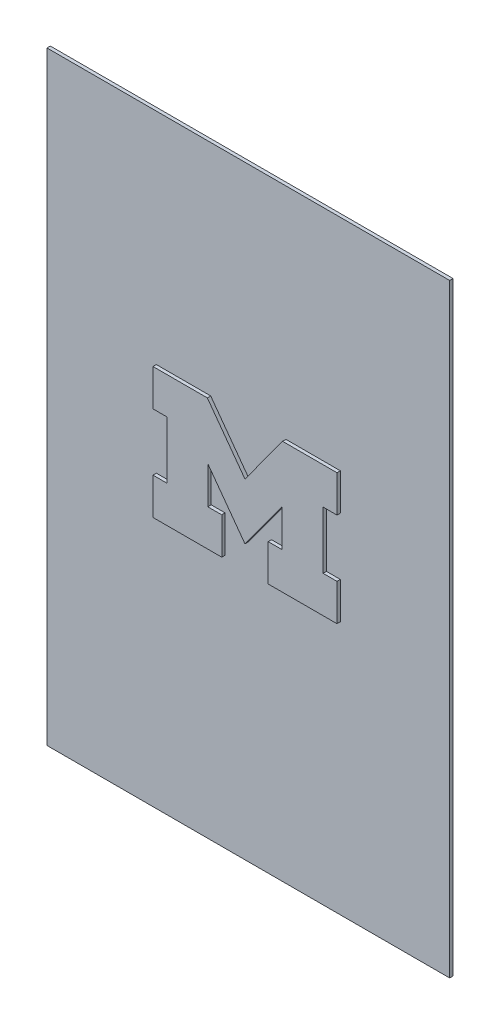
SolidWorks part; units mm, degrees
ref_plane "Front Plane" through (0, 0, 0) normal (0, 0, 1) x (1, 0, 0)
ref_plane "Top Plane" through (0, 0, 0) normal (0, 1, 0) x (1, 0, 0)
ref_plane "Right Plane" through (0, 0, 0) normal (1, 0, 0) x (0, 0, -1)
sketch "Sketch1" plane through (0, 0, 0) normal (0, 0, 1) x (1, 0, 0)
  line L1 (0, 0) -> (304.8, 0)
  line L2 (0, 0) -> (0, 457.2)
  line L3 (0, 457.2) -> (304.8, 457.2)
  line L4 (304.8, 0) -> (304.8, 457.2)
  dimension "D1" = 457.2
  dimension "D2" = 304.8
extrude "Boss-Extrude1" add sketch "Sketch1" along normal blind 2.54
sketch "Sketch3" plane through (0, 0, 2.54) normal (0, 0, 1) x (1, 0, 0)
  line L0 (152.4, 252.0909) -> (152.4, 457.2) construction
  line L1 (304.8, 457.2) -> (0, 457.2) construction
  line L2 (152.4, 457.2) -> (0, 457.2) construction
  line L24 (82.7659, 219.8748) -> (82.7659, 192.1117)
  line L25 (82.7659, 291.0718) -> (82.7659, 263.3088)
  line L26 (180.4797, 248.0688) -> (152.4, 209.6439)
  line L27 (222.0341, 291.0718) -> (222.0341, 263.3088)
  line L28 (93.2815, 263.3088) -> (93.2815, 219.8748)
  line L29 (211.5185, 263.3088) -> (211.5185, 219.8748)
  line L30 (134.8359, 219.8748) -> (124.3203, 219.8748)
  line L31 (134.8359, 192.1117) -> (134.8359, 219.8748)
  line L32 (82.7659, 263.3088) -> (93.2815, 263.3088)
  line L33 (124.3203, 248.0688) -> (152.4, 209.6439)
  line L34 (124.3203, 219.8748) -> (124.3203, 248.0688)
  line L35 (222.0341, 263.3088) -> (211.5185, 263.3088)
  line L36 (169.9641, 219.8748) -> (180.4797, 219.8748)
  line L37 (152.4, 252.0909) -> (123.9139, 291.0718)
  line L38 (180.4797, 219.8748) -> (180.4797, 248.0688)
  line L39 (180.8861, 291.0718) -> (222.0341, 291.0718)
  line L40 (211.5185, 219.8748) -> (222.0341, 219.8748)
  line L41 (152.4, 252.0909) -> (180.8861, 291.0718)
  line L42 (222.0341, 219.8748) -> (222.0341, 192.1117)
  line L43 (82.7659, 192.1117) -> (134.8359, 192.1117)
  line L44 (169.9641, 192.1117) -> (169.9641, 219.8748)
  line L45 (222.0341, 192.1117) -> (169.9641, 192.1117)
  line L46 (93.2815, 219.8748) -> (82.7659, 219.8748)
  line L47 (123.9139, 291.0718) -> (82.7659, 291.0718)
  dimension "D1" = 72.316
  dimension "D2" = 52.07
  dimension "D3" = 10.5156
  dimension "D4" = 41.148
  dimension "D5" = 28.194
  dimension "D6" = 43.434
  dimension "D7" = 25.0444
  dimension "D8" = 35.1282
extrude "Boss-Extrude3" add sketch "Sketch3" along normal blind 2.54 contours L37 L47 L25 L32 L28 L46 L24 L43 L31 L30 L34 L33 L26 L38 L36 L44 L45 L42 L40 L29 L35 L27 L39 L41 region at (152.4, 241.537, 2.54)
